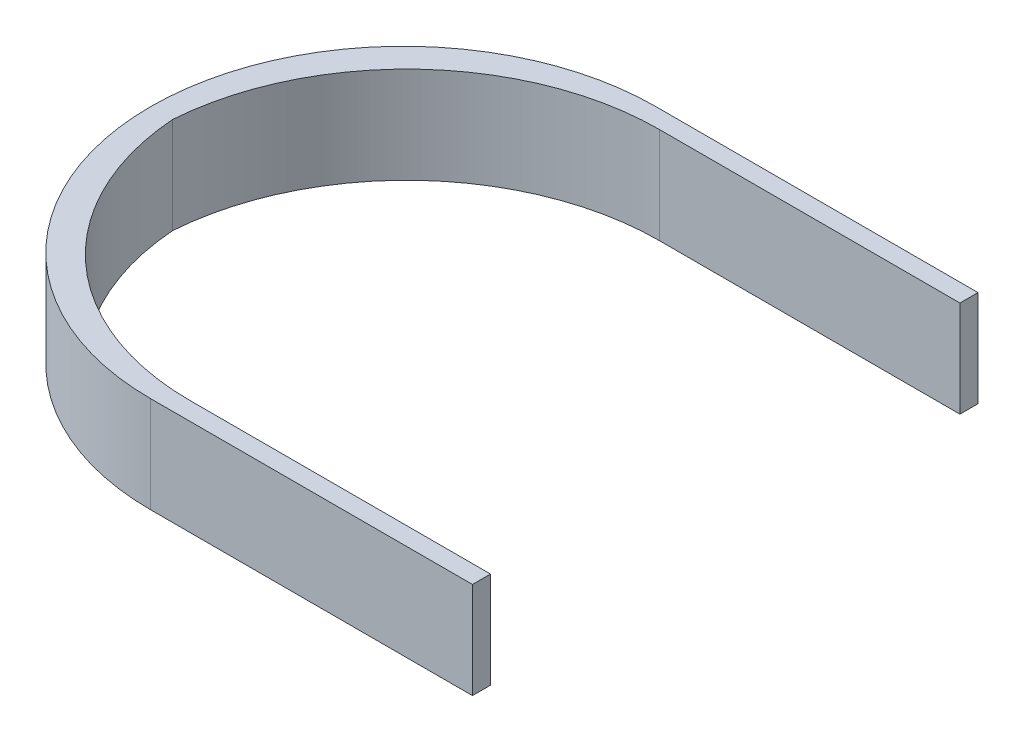
SolidWorks part; units mm, degrees
ref_plane "Alzado" through (0, 0, 0) normal (0, 0, 1) x (1, 0, 0)
ref_plane "Planta" through (0, 0, 0) normal (0, 1, 0) x (1, 0, 0)
ref_plane "Vista lateral" through (0, 0, 0) normal (1, 0, 0) x (0, 0, -1)
sketch "Croquis3" plane through (0, 0, 0) normal (0, 1, 0) x (1, 0, 0)
  line L1 (0, 0) -> (50, 0)
  line L2 (0, 0) -> (0, 42)
  line L3 (0, 42) -> (50, 42)
  line L4 (50, 0) -> (50, 42)
  line L7 (1.7857, 40.5) -> (48.2143, 40.5)
  line L8 (1.7857, 40.5) -> (1.7857, 1.5)
  line L9 (1.7857, 1.5) -> (48.2143, 1.5)
  line L10 (48.2143, 40.5) -> (48.2143, 1.5)
  point P5 (25, 21)
  dimension "D1" = 42
  dimension "D2" = 50
  dimension "D3" = 39
extrude "Saliente-Extruir7" add sketch "Croquis3" along normal blind 8 contours L2 L3 L4 L1
extrude "Cortar-Extruir2" cut sketch "Croquis3<13>" against normal blind 8 and the other way blind 8 contours L8 L9 L10 L7
sketch "Croquis3<13>" plane through (0, 0, 0) normal (0, 1, 0) x (1, 0, 0) same geometry as "Croquis3"
fillet "Redondeo3" radius 21 4 edges at (0, 4, 0) (1.7857, 4, -1.5) (1.7857, 4, -40.5) (0, 4, -42)
sketch "Croquis7" plane through (0, 8, 0) normal (0, 1, 0) x (1, 0, 0)
  line L1 (47.7497, 43.2268) -> (47.7497, -2.7885)
  line L2 (51.1433, -2.7885) -> (51.1433, 43.2268)
  line L3 (51.1433, 43.2268) -> (47.7497, 43.2268)
  line L4 (47.7497, -2.7885) -> (51.1433, -2.7885)
extrude "Cortar-Extruir3" cut sketch "Croquis7" against normal blind 8
